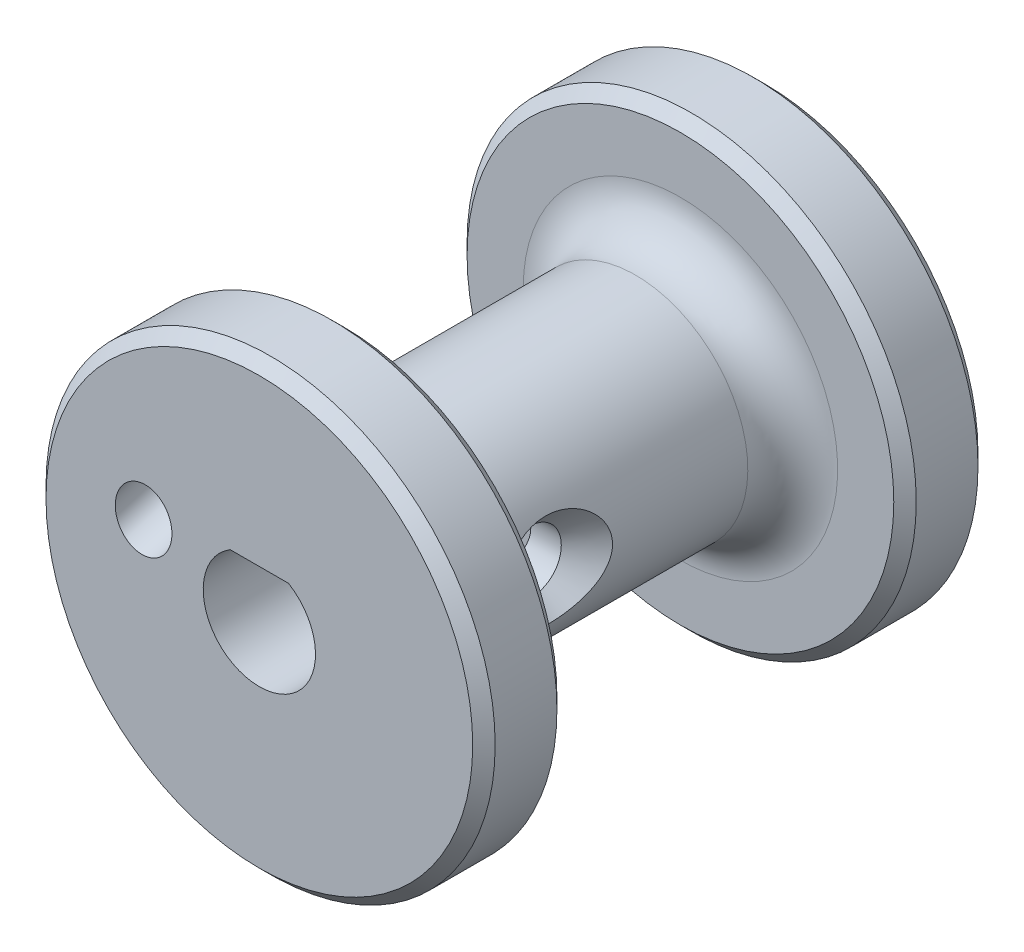
SolidWorks part; units mm, degrees
ref_plane "Front Plane" through (0, 0, 0) normal (0, 0, 1) x (1, 0, 0)
ref_plane "Top Plane" through (0, 0, 0) normal (0, 1, 0) x (1, 0, 0)
ref_plane "Right Plane" through (0, 0, 0) normal (1, 0, 0) x (0, 0, -1)
sketch "Sketch1" plane through (0, 0, 0) normal (0, 0, 1) x (1, 0, 0)
  circle A0 centre (0, 0) radius 3.175
  circle A1 centre (0, 0) radius 6.35
  dimension "D1" = 6.35
  dimension "D2" = 12.7
extrude "Boss-Extrude1" add sketch "Sketch1" along normal blind 9.525 and the other way blind 9.525 contours A1 A0 region at (-6.1704, 0, 0)
sketch "Sketch2" plane through (0, 0, -9.525) normal (0, 0, -1) x (-1, 0, 0)
  circle A0 centre (0, 0) radius 12.7
  circle A1 centre (0, 0) radius 6.35 construction
  circle A2 centre (0, 0) radius 6.35 construction
  circle A3 centre (0, 0) radius 3.175 construction
  circle A4 centre (0, 0) radius 3.175
  circle M3 centre (0, 0) radius 3.175
  circle M4 centre (0, 0) radius 6.35
  dimension "D1" = 6.35
extrude "Boss-Extrude3" add sketch "Sketch2" along normal blind 4.7625 contours M4 M3 | A0 M4 region at (12.3408, 0, -9.525) region at (6.1704, 0, -9.525)
mirror "Mirror1" about plane through (0, 0, 0) normal (0, 0, 1) of "Boss-Extrude3"
sketch "Sketch3" plane through (0, 0, -14.2875) normal (0, 0, -1) x (-1, 0, 0)
  circle A0 centre (0, 0) radius 3.175 construction
  circle A1 centre (0, 0) radius 3.175
extrude "Boss-Extrude4" add sketch "Sketch3" against normal through all
fillet "Fillet1" radius 2.54 2 edges at (6.35, 0, 9.525) (6.35, 0, -9.525)
chamfer "Chamfer1" distance 0.635 angle 45 4 edges at (-12.7, 0, -14.2875) (-12.7, 0, -9.525) (-12.7, 0, 9.525) (-12.7, 0, 14.2875)
sketch "Sketch4" plane through (0, 0, 14.2875) normal (0, 0, 1) x (1, 0, 0)
  line L0 (-1.651, 2.712) -> (1.651, 2.712)
  circle A3 centre (0, 0) radius 6.35
  circle A4 centre (0, 0) radius 6.35
  circle A5 centre (0, 0) radius 3.175
  circle A6 centre (0, 0) radius 3.175
  dimension "D1" = 0
  dimension "D3" = 3.302
  dimension "D2" = 0
extrude "Cut-Extrude1" cut sketch "Sketch4" against normal blind 13.97 contours L0 A6 region at (0, -0.0979, 14.2875)
sketch "Sketch5" plane through (0, 0, 14.2875) normal (0, 0, 1) x (1, 0, 0)
  point P0 (-6.5447, 1.737)
  point P1 (-6.5447, 1.737)
sketch3d "3DSketch1"
  point P0 (-5.8259, 4.2649, 8.8989)
ref_axis "Axis1" through (-5.8259, 4.2649, 8.8989) along (-0.1199, -0.4216, 0.8988)
ref_plane "Plane1" through (-6.5447, 1.737, 14.2875) normal (-0.1199, -0.4216, 0.8988) x (0.9928, -0.0509, 0.1085)
sketch "Sketch6" plane through (-6.5447, 1.737, 14.2875) normal (-0.1199, -0.4216, 0.8988) x (0.9928, -0.0509, 0.1085)
  circle A0 centre (0, 0) radius 1.5875
  dimension "D1" = 3.175
extrude "Cut-Extrude2" cut sketch "Sketch6" against normal up to next and the other way up to next
ref_plane "Plane2" through (6.35, 0, 0) normal (1, 0, 0) x (0, 0, -1)
sketch "Sketch7" plane through (6.35, 0, 0) normal (1, 0, 0) x (0, 0, -1)
  line L0 (-14.2875, 12.065) -> (-14.2875, -12.065) construction
  point P0 (-5.3975, 0)
  point P1 (0, 0)
  dimension "D1" = 8.89
ref_point "Point1"
hole_wizard "CSK for M3 Flat Head Machine Screw1" positions "3DSketch8" profile "Sketch14" countersink size "M3" standard "ANSI Metric" end condition up to next
sketch3d "3DSketch8"
  point P0 (6.3461, 0.2223, 3.8113)
sketch "Sketch14" plane through (6.3461, 0.2223, 3.8113) normal (0, 0, 1) x (-0.035, 0.9994, 0)
  line L0 (0, 0) -> (0, 3.175)
  line L1 (0, 3.175) -> (1.7, 3.175)
  line L2 (1.7, 3.175) -> (1.7, 1.45)
  line L3 (1.7, 1.45) -> (3.15, 0)
  line L5 (3.15, 0) -> (0, 0)
  line L6 (-1.7, 1.45) -> (-3.15, 0) construction
  line L11 (0, -6.35) -> (0, 107.95) construction
  dimension "Thru Hole Dia." = 3.4
  dimension "Thru Hole Depth" = 3.175
  dimension "Near C'Sink Dia." = 6.3
  dimension "Near C'Sink Angle" = 90
